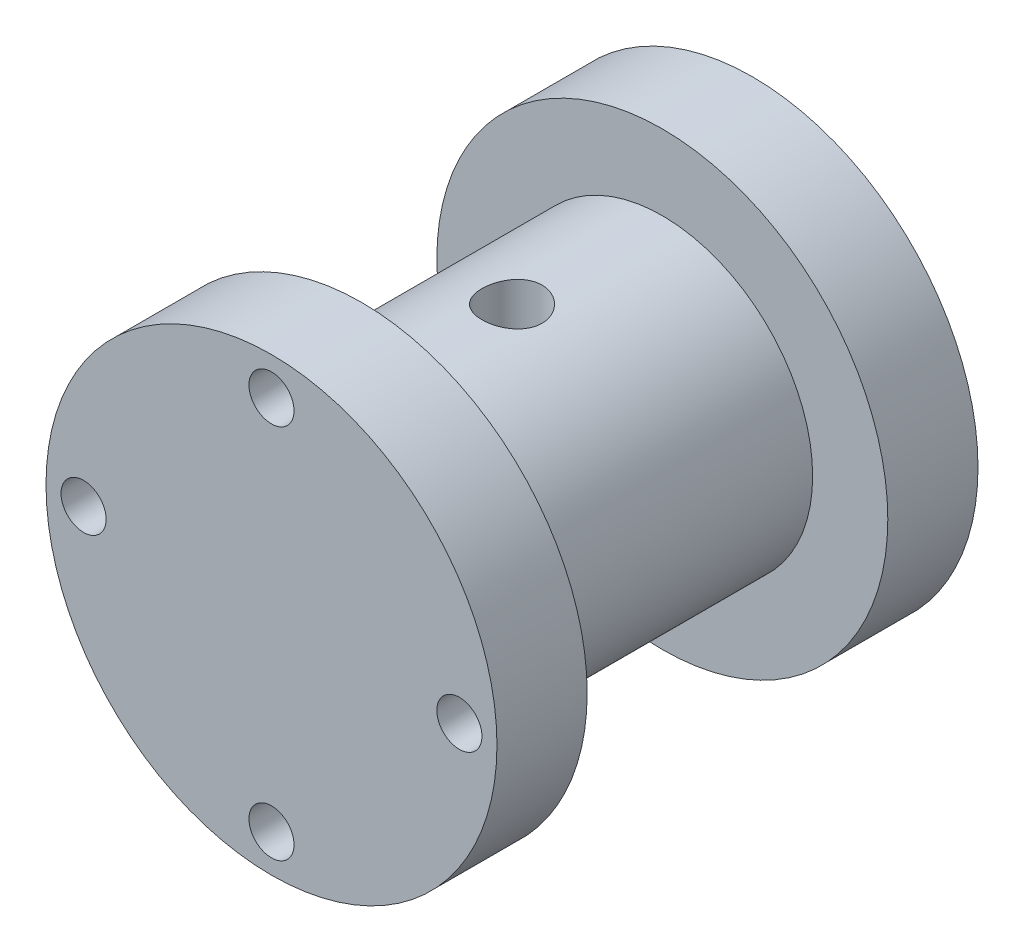
SolidWorks part; units mm, degrees
ref_plane "Front Plane" through (0, 0, 0) normal (0, 0, 1) x (1, 0, 0)
ref_plane "Top Plane" through (0, 0, 0) normal (0, 1, 0) x (1, 0, 0)
ref_plane "Right Plane" through (0, 0, 0) normal (1, 0, 0) x (0, 0, -1)
sketch "Sketch1" plane through (0, 0, 0) normal (0, 0, 1) x (1, 0, 0)
  circle A0 centre (0, 0) radius 5
  dimension "D1" = 10
extrude "Boss-Extrude1" add sketch "Sketch1" along normal blind 5 and the other way blind 5
sketch "Sketch3" plane through (0, 0, 5) normal (0, 0, 1) x (1, 0, 0)
  circle A0 centre (0, 0) radius 7.5
  dimension "D1" = 15
extrude "Boss-Extrude2" add sketch "Sketch3" along normal blind 3
mirror "Mirror1" about plane through (0, 0, 0) normal (0, 0, 1) of "Boss-Extrude2"
ref_plane "Plane1" through (0, 5, 0) normal (0, 1, 0) x (1, 0, 0)
sketch "Sketch4" plane through (0, 5, 0) normal (0, 1, 0) x (1, 0, 0)
  circle A0 centre (0, 0) radius 1
  dimension "D1" = 2
extrude "Cut-Extrude1" cut sketch "Sketch4" against normal through all contours A0
sketch "Sketch5" plane through (0, 0, 5) normal (0, 0, -1) x (-1, 0, 0)
  line L1 (0, 8.25) -> (0, -8.25) construction
  circle A0 centre (0, 6.25) radius 0.75
  circle A1 centre (0, 0) radius 7.5 construction
  dimension "D1" = 1.5
  dimension "D2" = 6.25
extrude "Cut-Extrude2" cut sketch "Sketch5" against normal through all
pattern_circular "CirPattern1" count 4 over 360 about axis through (0, 0, -5) along (0, 0, 1) of "Cut-Extrude2" reverse direction yes
